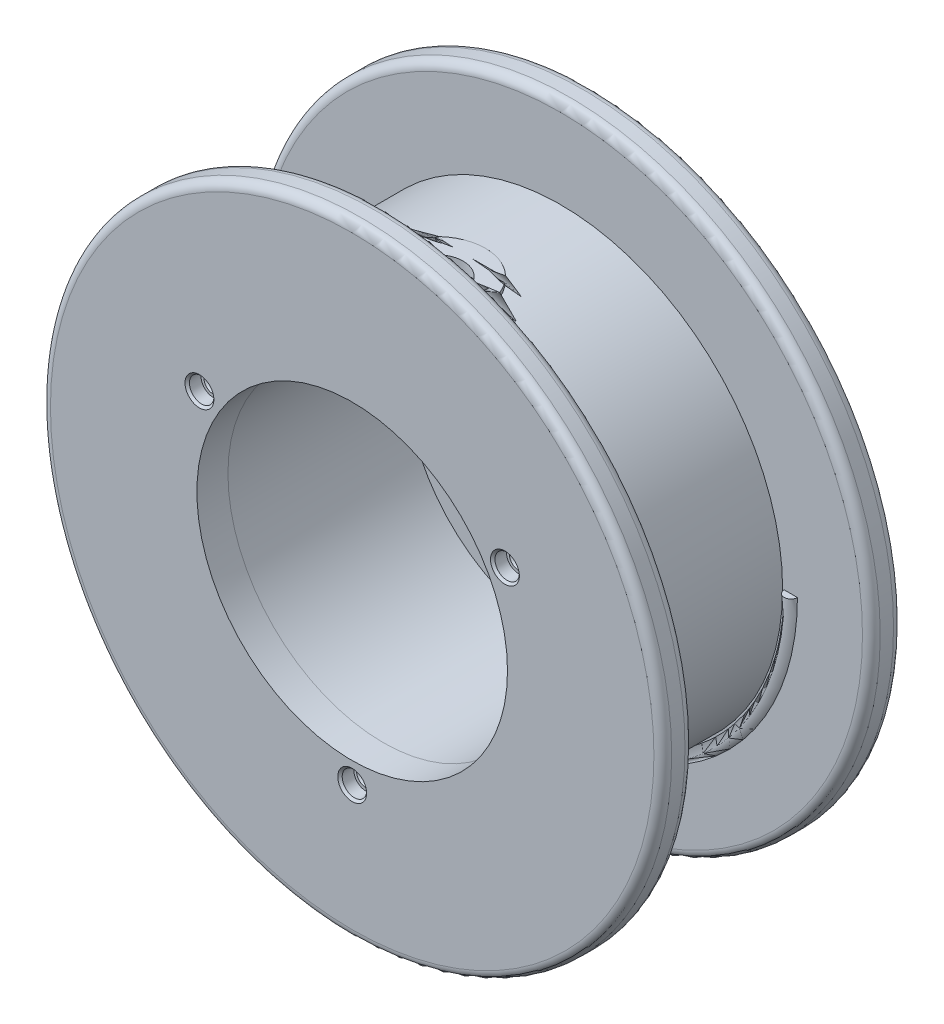
SolidWorks part; units mm, degrees
note: The reader was unsure of these and kept them because the rebuilt part matched: shared geometry of "Sketch2<3>", "Sketch3<3>", "Sketch3<5>", "Sketch6<4>", "Sketch6<7>", "Sketch9<3>".
other "Spool Body"
other "Spool Cover"
material "ABS"
ref_plane "Front Plane" through (0, 0, 0) normal (0, 0, 1) x (1, 0, 0)
ref_plane "Top Plane" through (0, 0, 0) normal (0, 1, 0) x (1, 0, 0)
ref_plane "Right Plane" through (0, 0, 0) normal (1, 0, 0) x (0, 0, -1)
sketch "Sketch1" plane through (0, 0, 0) normal (0, 0, 1) x (1, 0, 0)
  circle A0 centre (0, 0) radius 50
  dimension "D1" = 100
extrude "Boss-Extrude1" add sketch "Sketch1" along normal mid plane 40
sketch "Sketch2" plane through (0, 0, 0) normal (0, 0, 1) x (1, 0, 0)
  circle A0 centre (0, 0) radius 70
  circle A1 centre (0, 0) radius 50 construction
  dimension "D1" = 20
extrude "Boss-Extrude2" add sketch "Sketch2" against normal blind 7 from surface at -20 contours A0 starting at face at (50, 0, -20)
extrude "Boss-Extrude3" add sketch "Sketch2<3>" along normal blind 7 from surface at 20 starting at face at (50, 0, 20)
sketch "Sketch2<3>" plane through (0, 0, 0) normal (0, 0, 1) x (1, 0, 0) same geometry as "Sketch2"
sketch "Sketch3" plane through (0, 0, 0) normal (0, 1, 0) x (1, 0, 0)
  line L0 (0, 27) -> (0, -27) construction
  line L1 (70, 27) -> (-70, 27) construction
  line L2 (-70, -27) -> (70, -27) construction
  line L4 (70, -20) -> (-70, -20) construction
  line L5 (-2.3077, -13.5385) -> (0, -14.5)
  line L6 (0, -14.5) -> (2.3077, -13.5385)
  arc A0 (2.3077, -13.5385) -> (-2.3077, -13.5385) centre (0, -8) ccw
  circle A1 centre (0, -8) radius 11
  dimension "D1" = 12
  dimension "D2" = 5
  dimension "D3" = 1
  dimension "D4" = 0.5
extrude "Cut-Extrude1" cut sketch "Sketch3" along normal through all contours A0 L0 | L0 A0
extrude "Boss-Extrude4" add sketch "Sketch3<3>" against normal up to surface from offset 50
sketch "Sketch3<3>" plane through (0, 0, 0) normal (0, 1, 0) x (1, 0, 0) same geometry as "Sketch3"
sketch "Sketch4" plane through (0, 0, 27) normal (0, 0, 1) x (1, 0, 0)
  circle A1 centre (0, 0) radius 50 construction
  circle A2 centre (0, 0) radius 35
  circle A3 centre (0, 0) radius 50 construction
  dimension "D1" = 15
extrude "Cut-Extrude2" cut sketch "Sketch4" against normal up to surface (47 mm away) up to face at (50, 0, -20)
extrude "Boss-Extrude8" add sketch "Sketch3<5>" along normal up to surface (3 mm away) from offset 32
sketch "Sketch3<5>" plane through (0, 0, 0) normal (0, 1, 0) x (1, 0, 0) same geometry as "Sketch3"
sketch "Sketch6" plane through (0, 0, 0) normal (0, 0, 1) x (1, 0, 0)
  circle A0 centre (0, 0) radius 14.25 construction
  circle A1 centre (0, 0) radius 15 construction
  circle A2 centre (0, 15) radius 2.1
  circle A3 centre (0, 15) radius 3.5
  circle A4 centre (0, -14.25) radius 2.1
  dimension "D1" = 28.5
  dimension "D2" = 30
  dimension "D3" = 4.2
  dimension "D4" = 7
  dimension "D5" = 4.2
extrude "Cut-Extrude5" cut sketch "Sketch6" against normal through all contours A2
extrude "Cut-Extrude6" cut sketch "Sketch6<4>" along normal blind 3.5 from surface at -27 contours A4 starting at face at (2.1, 15, -27)
sketch "Sketch6<4>" plane through (0, 0, 0) normal (0, 0, 1) x (1, 0, 0) same geometry as "Sketch6"
extrude "Boss-Extrude9" add sketch "Sketch6<7>" along normal blind 6 from surface at -20 contours A3 A2 starting at face at (2.1, 15, -20)
sketch "Sketch6<7>" plane through (0, 0, 0) normal (0, 0, 1) x (1, 0, 0) same geometry as "Sketch6"
chamfer "Chamfer2" distance 3 angle 45 1 edges at (0, 32, 19)
fillet "Fillet1" radius 3 1 edges at (3.5, 15, -20)
pattern_circular "CirPattern5" count 3 over 360 about axis through (0, 0, 0) along (0, 0, 1) of "Boss-Extrude9", "Cut-Extrude6", "Cut-Extrude5", "Fillet1"
fillet "Fillet2" radius 2 4 edges at (70, 0, 20) (70, 0, -20) (70, 0, -27) (70, 0, 27)
ref_plane "Plane1" through (0, 0, 20) normal (0, 0, -1) x (-1, 0, 0)
split "Split1" trim tools "Plane1" bodies to split 120 115 resulting bodies 117 118
sketch "Sketch9" plane through (0, 0, 0) normal (0, 0, 1) x (1, 0, 0)
  circle A0 centre (0, -39.75) radius 1.6
  circle A1 centre (0, -39.75) radius 2.75
  circle A3 centre (0, 0) radius 35 construction
  dimension "D1" = 3.2
  dimension "D2" = 5.5
  dimension "D3" = 2
extrude "Cut-Extrude7" cut sketch "Sketch9" along normal through all from surface at 20 contours A0 starting at face at (-35, 0, 20)
extrude "Cut-Extrude9" cut sketch "Sketch9<3>" against normal blind 3.1 from surface at 27 contours A1 A0 starting at face at (-1.6, -39.75, 27)
sketch "Sketch9<3>" plane through (0, 0, 0) normal (0, 0, 1) x (1, 0, 0) same geometry as "Sketch9"
chamfer "Chamfer3" distance 0.5 angle 45 2 edges at (2.75, -39.75, 27) (1.6, -39.75, 23.9)
pattern_circular "CirPattern6" count 3 over 360 about axis through (0, 0, 0) along (0, 0, 1) of "Cut-Extrude7", "Cut-Extrude9", "Chamfer3"
sketch "Sketch10" plane through (0, 0, 0) normal (0, 0, 1) x (1, 0, 0)
  circle A0 centre (0, -39.75) radius 1.4
  dimension "D1" = 2.8
extrude "Cut-Extrude10" cut sketch "Sketch10" against normal offset from surface (13.1 mm away) 17 from surface at 20 up to face at (2.1, -39.75, 23.9) starting at face at (50, 0, 20)
chamfer "Chamfer4" distance 0.5 angle 45 1 edges at (-1.4, -39.75, 20)
pattern_circular "CirPattern9" count 3 over 360 about axis through (0, 0, 0) along (0, 0, 1) of "Chamfer4", "Cut-Extrude10"
sketch "Sketch11" plane through (0, 0, -20) normal (0, 0, 1) x (1, 0, 0)
  circle A0 centre (0, 0) radius 52
  dimension "D1" = 104
curve "Helix/Spiral1" pitch 4.375 height 35 turns 8
sketch "Sketch13" plane through (0, 0, 0) normal (0, 1, 0) x (1, 0, 0)
  circle A1 centre (51.8392, 20.0192) radius 1.5
  dimension "D1" = 3
sweep "Sweep2" add profiles "Sketch13" path "Helix/Spiral1"
